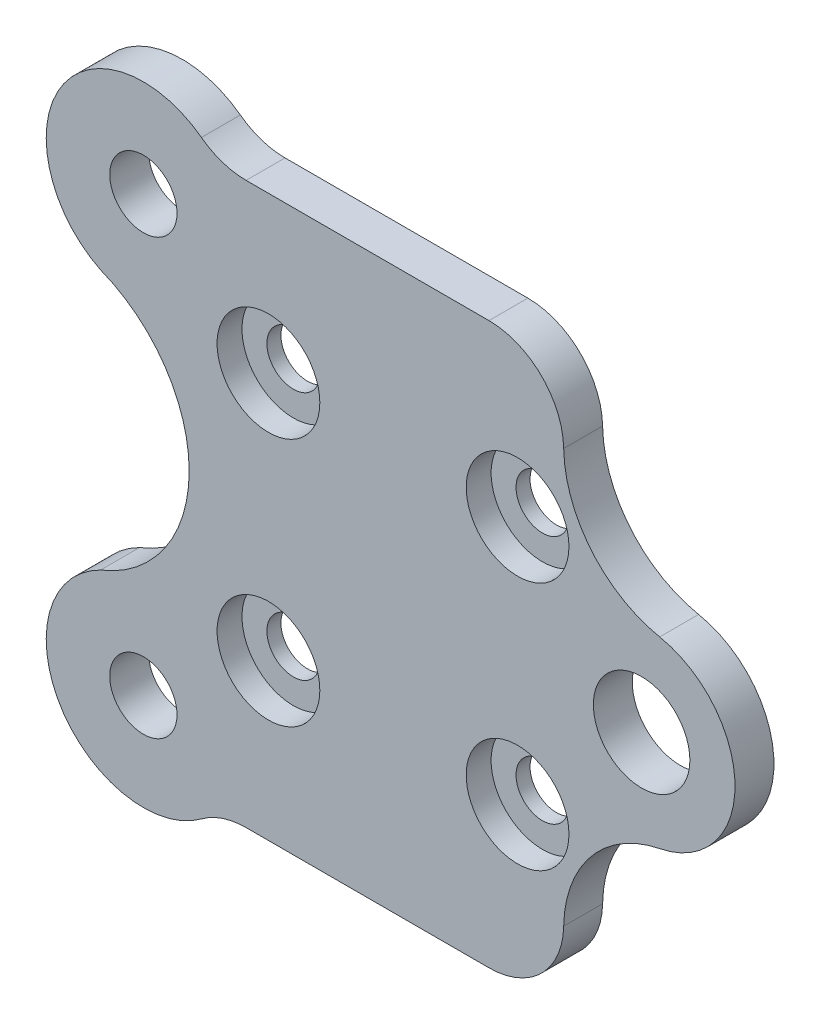
SolidWorks part; units mm, degrees
ref_plane "Front Plane" through (0, 0, 0) normal (0, 0, 1) x (1, 0, 0)
ref_plane "Top Plane" through (0, 0, 0) normal (0, 1, 0) x (1, 0, 0)
ref_plane "Right Plane" through (0, 0, 0) normal (1, 0, 0) x (0, 0, -1)
sketch "Model" plane through (0, 0, 0) normal (0, 0, 1) x (1, 0, 0)
  line L0 (57.9402, 39.9305) -> (85.7512, 39.9305)
  line L2 (85.7512, 0.7699) -> (85.7512, -5.0695)
  line L3 (85.7512, 39.9305) -> (85.7512, 34.0911)
  line L4 (57.9402, -5.0695) -> (85.7512, -5.0695)
  arc A0 (48.5736, 27.8627) -> (57.9402, 39.9305) centre (52.0082, 34.8658) cw
  circle A1 centre (92.0082, 17.4305) radius 3.875
  circle A2 centre (52.0082, -0.0048) radius 2.7
  circle A3 centre (52.0082, 34.8658) radius 2.7
  circle A4 centre (82.0501, 7.4305) radius 2.125
  circle A5 centre (62.0501, 7.4305) radius 2.125
  circle A6 centre (82.0501, 27.4305) radius 2.125
  circle A7 centre (62.0501, 27.4305) radius 2.125
  arc A8 (48.5736, 6.9983) -> (57.9402, -5.0695) centre (52.0082, -0.0048) ccw
  arc A11 (93.4574, 10.0719) -> (85.7512, 0.7699) centre (95.3556, 0.6562) ccw
  arc A12 (93.4574, 10.0719) -> (93.4574, 24.7892) centre (92.0082, 17.4305) ccw
  arc A13 (85.7512, 34.0911) -> (93.4574, 24.7892) centre (95.3556, 34.2048) ccw
  arc A16 (48.5736, 6.9983) -> (48.5736, 27.8627) centre (44.48, 17.4305) ccw
  circle A22 centre (62.0501, 27.4305) radius 4.125
  circle A23 centre (62.0501, 7.4305) radius 4.125
  circle A24 centre (82.0501, 27.4305) radius 4.125
  circle A25 centre (82.0501, 7.4305) radius 4.125
  dimension "D2" = 7.75
  dimension "D3" = 8.25
  dimension "D4" = 4.25
  dimension "D5" = 5.4
  dimension "D6" = 34.8706
  dimension "D7" = 9.9581
  dimension "D8" = 22.5
  dimension "D9" = 22.5
  dimension "D11" = 11.2066
  dimension "D12" = 7.8
  dimension "D18" = 9.6051
  dimension "D19" = 7.5
  dimension "D10" = 40
  dimension "D13" = 20
  dimension "D14" = 10
  dimension "D15" = 19.9999
  dimension "D16" = 47.5282
  dimension "D17" = 6.257
  dimension "D20" = 3.3474
  dimension "D21" = 16.7743
extrude "Boss-Extrude1" add sketch "Model" against normal blind 3.125 contours A3 | A2 | A1 | A7 | A6 | A4 | A5 | L4 L2 A11 A12 A13 L3 L0 A0 A16 A8 region at (92.0082, 17.4305, 0) region at (52.0082, -0.0048, 0) region at (52.0082, 34.8658, 0) region at (82.0501, 7.4305, 0) region at (62.0501, 7.4305, 0) region at (82.0501, 27.4305, 0) region at (62.0501, 27.4305, 0)
extrude "Cut-Extrude1" cut sketch "Model<3>" against normal blind 2 contours A25 A4 | A23 A5 | A22 A7 | A24 region at (58.0418, 27.4305, 0) region at (58.0418, 7.4305, 0) region at (78.0417, 7.4305, 0)
sketch "Model<3>" plane through (0, 0, 0) normal (0, 0, 1) x (1, 0, 0) same geometry as "Model"
fillet "Fillet1" radius 6 2 edges at (85.7512, -5.0695, -1.5625) (85.7512, 39.9305, -1.5625)
fillet "Fillet2" radius 6 2 edges at (57.9402, 39.9305, -1.5625) (57.9402, -5.0695, -1.5625)
